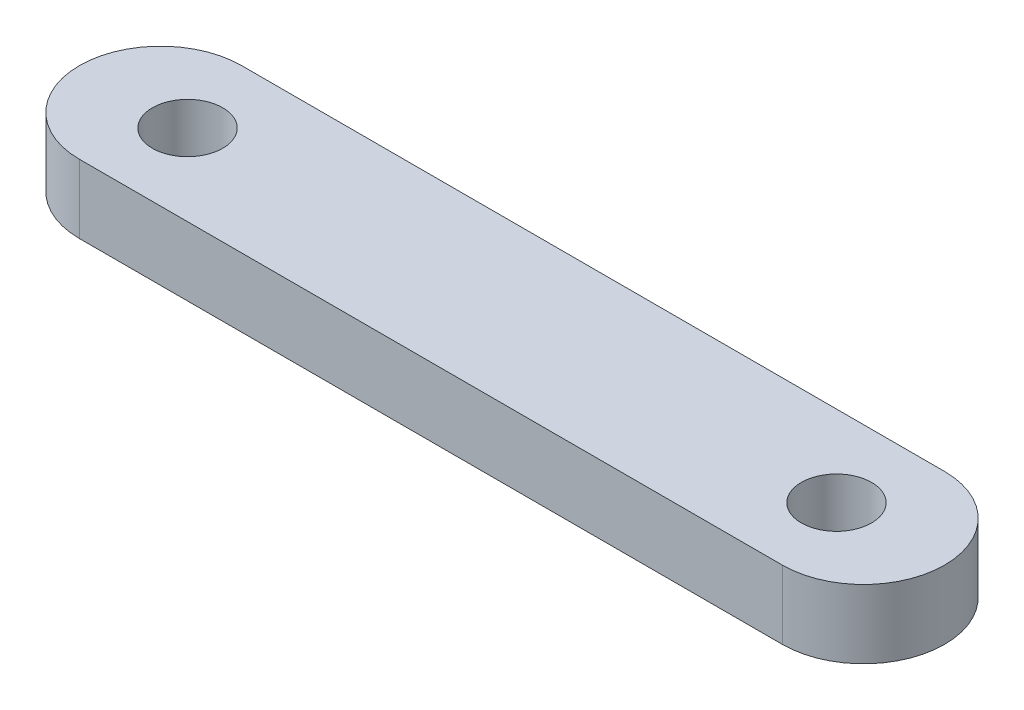
SolidWorks part; units mm, degrees
material "6061 Alloy"
ref_plane "Front Plane" through (0, 0, 0) normal (0, 0, 1) x (1, 0, 0)
ref_plane "Top Plane" through (0, 0, 0) normal (0, 1, 0) x (1, 0, 0)
ref_plane "Right Plane" through (0, 0, 0) normal (1, 0, 0) x (0, 0, -1)
sketch "Sketch1" plane through (0, 0, 0) normal (0, 1, 0) x (1, 0, 0)
  line L1 (-40, 7.5) -> (40, 7.5)
  line L2 (-40, 7.5) -> (-40, -7.5)
  line L3 (-40, -7.5) -> (40, -7.5)
  line L4 (40, 7.5) -> (40, -7.5)
  line L5 (-40, 7.5) -> (40, -7.5) construction
  line L6 (-40, -7.5) -> (40, 7.5) construction
  point P0 (0, 0)
  dimension "D1" = 80
  dimension "D2" = 15
extrude "Boss-Extrude1" add sketch "Sketch1" along normal blind 6.35
sketch "Sketch2" plane through (0, 6.35, 0) normal (0, 1, 0) x (1, 0, 0)
  line L0 (-40, 7.5) -> (-40, -7.5) construction
  line L1 (40, -7.5) -> (40, 7.5) construction
  circle A0 centre (-30, 0) radius 3.25
  circle A1 centre (30, 0) radius 3.25
  dimension "D1" = 6.5
  dimension "D2" = 10
  dimension "D3" = 10
extrude "Cut-Extrude1" cut sketch "Sketch2" against normal through all contours A0 | A1
fillet "Fillet1" 2 edges at (-40, 3.175, -7.5) (-40, 3.175, 7.5) type full round first side face at (0, 3.175, -7.5) second side face at (0, 3.175, 7.5) middle face at (-40, 3.175, 0)
fillet "Fillet2" 2 edges at (40, 3.175, -7.5) (40, 3.175, 7.5) type full round first side face at (3.75, 3.175, -7.5) second side face at (3.75, 3.175, 7.5) middle face at (40, 3.175, 0)
